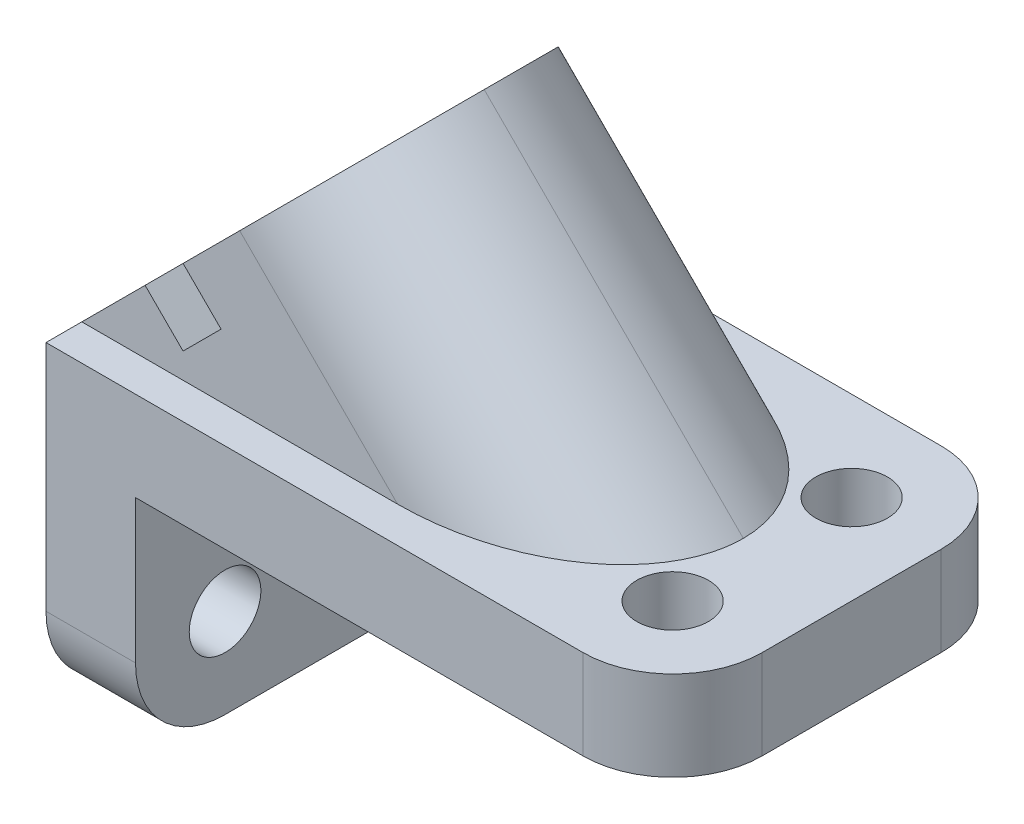
SolidWorks part; units mm, degrees
ref_plane "Front Plane" through (0, 0, 0) normal (0, 0, 1) x (1, 0, 0)
ref_plane "Top Plane" through (0, 0, 0) normal (0, 1, 0) x (1, 0, 0)
ref_plane "Right Plane" through (0, 0, 0) normal (1, 0, 0) x (0, 0, -1)
sketch "Sketch1" plane through (0, 0, 0) normal (0, 1, 0) x (1, 0, 0)
  line L1 (-75, 50) -> (75, 50)
  line L2 (-75, 50) -> (-75, -50)
  line L3 (-75, -50) -> (75, -50)
  line L4 (75, 50) -> (75, -50)
  line L5 (-75, 50) -> (75, -50) construction
  line L6 (-75, -50) -> (75, 50) construction
  point P0 (0, 0)
  dimension "D1" = 100
  dimension "D2" = 150
extrude "Boss-Extrude1" add sketch "Sketch1" along normal blind 25
sketch "Sketch2" plane through (-75, 0, 0) normal (-1, 0, 0) x (0, 0, 1)
  line L1 (-50, 25) -> (50, 25)
  line L2 (-50, 25) -> (-50, -65)
  line L3 (-50, -65) -> (50, -65)
  line L4 (50, 25) -> (50, -65)
  dimension "D1" = 90
extrude "Boss-Extrude2" add sketch "Sketch2" along normal blind 25
fillet "Fillet1" radius 25 4 edges at (-87.5, -65, -50) (-87.5, -65, 50) (75, 12.5, -50) (75, 12.5, 50)
sketch3d "3DSketch1" plane through (0, 0, 0) normal (0, 0, 1) x (1, 0, 0)
ref_plane "Plane1" through (-62.5, 62.5, 0) normal (0.7071, -0.7071, 0) x (0, 0, -1)
sketch "Sketch5" plane through (-62.5, 62.5, 0) normal (0.7071, -0.7071, 0) x (0, 0, -1)
  line L0 (-50, -53.033) -> (50, -53.033) construction
  line L1 (-40, 49.3254) -> (40, 49.3254)
  line L2 (-40, 49.3254) -> (-40, -53.033)
  line L3 (-40, -53.033) -> (40, -53.033)
  line L4 (40, 49.3254) -> (40, -53.033)
  line L5 (-50, -53.033) -> (-50, 53.033) construction
  dimension "D1" = 80
  dimension "D2" = 102.3584
  dimension "D3" = 0
  dimension "D4" = 10
extrude "Boss-Extrude3" add sketch "Sketch5" along normal up to next
sketch "Sketch6" plane through (-62.5, 62.5, 0) normal (-0.7071, 0.7071, 0) x (0, 0, 1)
  line L0 (-40, 49.3254) -> (-40, -53.033) construction
  line L1 (-40, -13.033) -> (40, -13.033)
  line L2 (-40, -13.033) -> (-40, -28.033)
  line L3 (-40, -28.033) -> (40, -28.033)
  line L4 (40, -13.033) -> (40, -28.033)
  line L5 (40, 49.3254) -> (40, -53.033) construction
  line L6 (40, -53.033) -> (-40, -53.033) construction
  dimension "D1" = 25
  dimension "D2" = 15
extrude "Cut-Extrude1" cut sketch "Sketch6" against normal blind 15
sketch "Sketch7" plane through (-62.5, 62.5, 0) normal (-0.7071, 0.7071, 0) x (0.7071, 0.7071, 0)
  line L0 (-13.033, -40) -> (-13.033, 40) construction
  circle A0 centre (21.967, 0) radius 15
  dimension "D1" = 30
  dimension "D2" = 35
extrude "Cut-Extrude2" cut sketch "Sketch7" against normal through all
sketch "Sketch8" plane through (0, 25, 0) normal (0, 1, 0) x (1, 0, 0)
  circle A0 centre (50, 25) radius 10
  circle A1 centre (50, -25) radius 10
  dimension "D1" = 20
  dimension "D2" = 20
extrude "Cut-Extrude3" cut sketch "Sketch8" against normal through all
sketch "Sketch9" plane through (-100, 0, 0) normal (-1, 0, 0) x (0, 0, 1)
  circle A0 centre (-25, -40) radius 10
  circle A1 centre (25, -40) radius 10
  dimension "D1" = 20
  dimension "D2" = 20
extrude "Cut-Extrude4" cut sketch "Sketch9" against normal through all
fillet "Fillet4" radius 40 2 edges at (8.5674, 61.1891, -40) (8.5674, 61.1891, 40)
